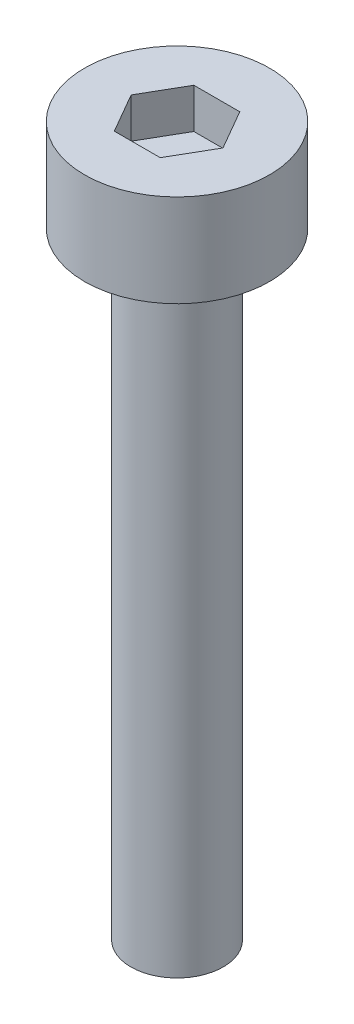
SolidWorks part; units mm, degrees
ref_plane "Front Plane" through (0, 0, 0) normal (0, 0, 1) x (1, 0, 0)
ref_plane "Top Plane" through (0, 0, 0) normal (0, 1, 0) x (1, 0, 0)
ref_plane "Right Plane" through (0, 0, 0) normal (1, 0, 0) x (0, 0, -1)
sketch "Sketch1" plane through (0, 0, 0) normal (0, 1, 0) x (1, 0, 0)
  circle A0 centre (0, 0) radius 1.5
  dimension "D1" = 3
extrude "ScrewShaft" add sketch "Sketch1" along normal blind 20
sketch "Sketch2" plane through (0, 20, 0) normal (0, 1, 0) x (1, 0, 0)
  circle A0 centre (0, 0) radius 3
  dimension "D1" = 6
extrude "Boss-Extrude2" add sketch "Sketch2" along normal blind 3
sketch "Sketch3" plane through (0, 23, 0) normal (0, 1, 0) x (1, 0, 0)
  line L0 (0, 0) -> (0, 1.29) construction
  line L1 (1.4896, 0) -> (0.7448, 1.29)
  line L2 (0.7448, 1.29) -> (-0.7448, 1.29)
  line L3 (-0.7448, 1.29) -> (-1.4896, 0)
  line L4 (-1.4896, 0) -> (-0.7448, -1.29)
  line L5 (-0.7448, -1.29) -> (0.7448, -1.29)
  line L6 (0.7448, -1.29) -> (1.4896, 0)
  circle A0 centre (0, 0) radius 1.29 construction
  dimension "D1" = 2.58
extrude "Cut-Extrude1" cut sketch "Sketch3" against normal blind 1.3
equation "\"X-ROD-SPACING\"=45"
equation "\"Y-ROD-SPACING\"=75"
equation "\"Z-ROD-SPACING\"=17.5"
equation "\"Y-BED-OFFSET\"=2"
equation "\"Y-BED-ROD-INSET\"=3.5"
equation "\"T-SLOT-NUT-FILLET-RADIUS\"=0.25"
equation "\"T-SLOT-SCREW-SHAFT-RADIUS\"=1.75"
equation "\"T-SLOT-SCREW-SHAFT-CUTOUT-LENGTH\"=10.5"
equation "\"T-SLOT-NUT-DEPTH\"=4.2"
equation "\"T-SLOT-NUT-WIDTH\"=3"
equation "\"T-SLOT-NUT-END-DISTANCE\"=8"
equation "\"ACRYLIC-THICKNESS\"=10"
equation "\"ACRYLIC-THICKNESS2\"=4.5"
equation "\"ACRYLIC-TAB-CUTOUT-SIZE\"=\"ACRYLIC-THICKNESS\"+\"ACRYLIC-TAB-TOLERANCE\"*2"
equation "\"ACRYLIC-TAB-WIDTH\"=\"ACRYLIC-THICKNESS\""
equation "\"ACRYLIC-M3-HOLE\"=3.1"
equation "\"SMOOTHROD-CAP-SCREW-DISTANCE\"=20"
equation "\"FRAME-WIDTH-INNER\"=370"
equation "\"NEMA17-HOLE-SPACING\"=31"
equation "\"NEMA17-CENTRAL-CUTOUT\"=22.5"
equation "\"Z-BRACKET-REACH\"=55"
equation "\"TOP-BRACKET-SPACING\"=40"
equation "\"SMOOTHROD-X-LENGTH\"=350"
equation "\"SMOOTHROD-Y-LENGTH\"=350"
equation "\"SMOOTHROD-Z-LENGTH\"=350"
equation "\"SMOOTHROD-TIGHTENING-HEADROOM\"=.25"
equation "\"LEADSCREW-Z-LENGTH\"=300"
equation "\"SCREW-LENGTH-FRAME\"=\"ACRYLIC-THICKNESS\" + 10"
equation "\"SCREW-HEAD-RADIUS\"=6"
equation "\"PRINTED-X-SMOOTHROD-DIAMETER\"=8.2"
equation "\"PRINTED-X-SMOOTHROD-CUTOUT\"=10"
equation "\"PRINTED-X-BASE-HEIGHT\"=10"
equation "\"PRINTED-LM8UU-CUTOUT-SIZE\"=15.25"
equation "\"PRINTED-LM8UU-CUTOUT-LENGTH\"=24.5"
equation "\"PRINTED-X-IDLER-HEIGHT\"=16"
equation "\"PSU-MOUNTING-WIDTH\"=95"
equation "\"PSU-MOUNTING-HEIGHT\"=177"
equation "\"D1@ScrewShaft\"=\"SCREW-LENGTH-FRAME\""
equation "\"D1@Sketch2\"=\"SCREW-HEAD-RADIUS\""
